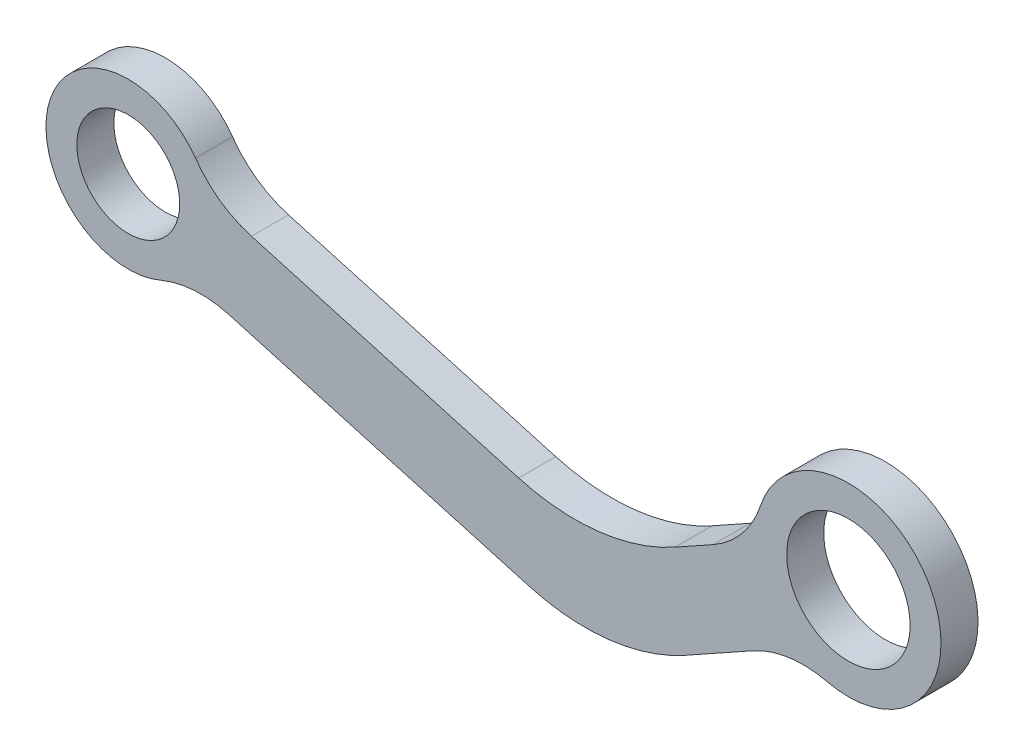
SolidWorks part; units mm, degrees
material "2018 合金"
ref_plane "正面" through (0, 0, 0) normal (0, 0, 1) x (1, 0, 0)
ref_plane "平面" through (0, 0, 0) normal (0, 1, 0) x (1, 0, 0)
ref_plane "右側面" through (0, 0, 0) normal (1, 0, 0) x (0, 0, -1)
sketch "ｽｹｯﾁ1" plane through (0, 0, 0) normal (0, 0, 1) x (1, 0, 0)
  line L0 (0, 0) -> (35, 0) construction
  circle A0 centre (0, 0) radius 2.5
  circle A1 centre (35, 0) radius 3
  circle A2 centre (35, 0) radius 4.5
  circle A3 centre (0, 0) radius 4
  dimension "D1" = 35
  dimension "D2" = 6
  dimension "D3" = 1.5
  dimension "D4" = 5
  dimension "D5" = 8
extrude "ﾎﾞｽ - 押し出し1" add sketch "ｽｹｯﾁ1" along normal blind 1.8
sketch "ｽｹｯﾁ3" plane through (0, 0, 1.8) normal (0, 0, 1) x (1, 0, 0)
  line L0 (35, 0) -> (23.2124, -6.5805) construction
  line L1 (23.2124, -6.5805) -> (0, 0) construction
  line L2 (30.5053, -0.2186) -> (22.9609, -4.4303)
  line L3 (22.9609, -4.4303) -> (3.8783, 0.9794)
  line L4 (32.4551, -3.7113) -> (23.4639, -8.7306)
  line L5 (23.4639, -8.7306) -> (2.7873, -2.869)
  line L7 (23.4639, -8.7306) -> (-0.5455, -1.9242) construction
  line L8 (22.9609, -4.4303) -> (0.5455, 1.9242) construction
  line L9 (34.0251, 1.7463) -> (22.9609, -4.4303) construction
  line L10 (35.9749, -1.7463) -> (23.4639, -8.7306) construction
  circle A2 centre (35, 0) radius 3 construction
  circle A3 centre (0, 0) radius 4 construction
  circle A4 centre (35, 0) radius 4.5 construction
  arc A5 (2.7873, -2.869) -> (3.8783, 0.9794) centre (0, 0) ccw
  arc A6 (30.5053, -0.2186) -> (32.4551, -3.7113) centre (35, 0) ccw
  point P1 (35, 0)
  dimension "D1" = 135
  dimension "D3" = 2
  dimension "D2" = 2
  dimension "D4" = 13.5
extrude "ﾎﾞｽ - 押し出し2" add sketch "ｽｹｯﾁ3" against normal up to surface (1.8 mm away) up to face at (4, 0, 0)
fillet "ﾌｨﾚｯﾄ1" radius 10 2 edges at (22.9609, -4.4303, 0.9) (23.4639, -8.7306, 0.9)
fillet "ﾌｨﾚｯﾄ2" radius 5 4 edges at (32.4551, -3.7113, 0.9) (30.5053, -0.2186, 0.9) (3.8783, 0.9794, 0.9) (2.7873, -2.869, 0.9)
